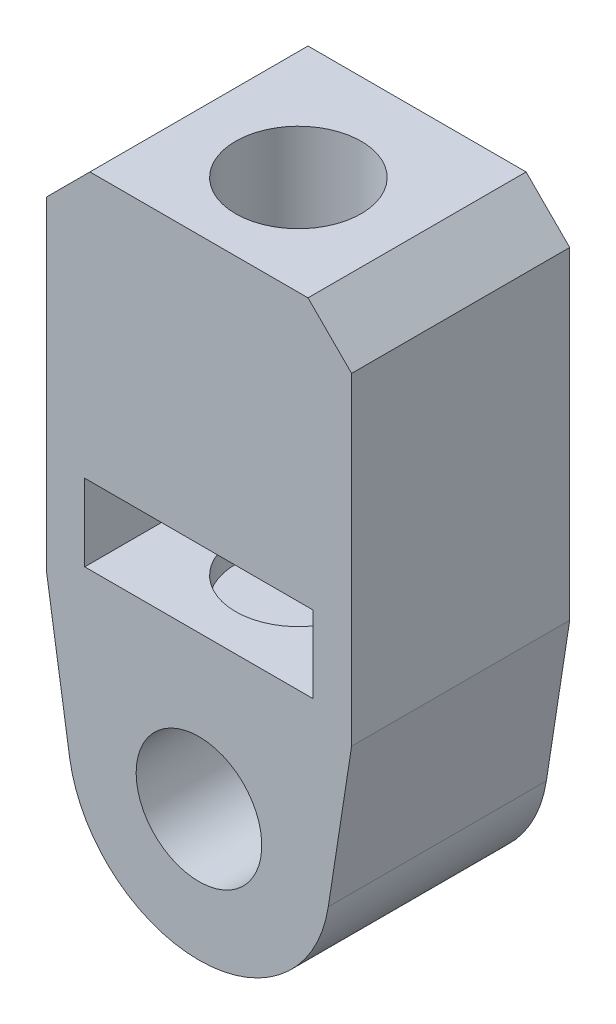
SolidWorks part; units mm, degrees
ref_plane "Front Plane" through (0, 0, 0) normal (0, 0, 1) x (1, 0, 0)
ref_plane "Top Plane" through (0, 0, 0) normal (0, 1, 0) x (1, 0, 0)
ref_plane "Right Plane" through (0, 0, 0) normal (1, 0, 0) x (0, 0, -1)
sketch "Sketch1" plane through (0, 0, 0) normal (0, 0, 1) x (1, 0, 0)
  line L0 (-5.5562, 4.7625) -> (-5.5562, 18.0975)
  line L1 (-5.5562, 18.0975) -> (5.5562, 18.0975)
  line L2 (5.5562, 18.0975) -> (5.5562, 4.7625)
  line L3 (-5.5562, 4.7625) -> (-4.7065, -0.7284)
  line L4 (4.7065, -0.7284) -> (5.5562, 4.7625)
  circle A1 centre (0, 0) radius 2.286
  arc A2 (-4.7065, -0.7284) -> (4.7065, -0.7284) centre (0, 0) ccw
  point P10 (0, 18.0975)
  dimension "D1" = 9.525
  dimension "D2" = 4.572
  dimension "D3" = 13.335
  dimension "D4" = 11.1125
  dimension "D5" = 4.7625
extrude "Boss-Extrude1" add sketch "Sketch1" along normal up to surface (7.9375 mm away)
sketch "Sketch2" plane through (0, 18.0975, 0) normal (0, 1, 0) x (1, 0, 0)
  circle A1 centre (0, -4.3187) radius 2.286
  circle A2 centre (0, -4.3187) radius 1.7525 construction
  dimension "D1" = 4.572
extrude "Cut-Extrude1" cut sketch "Sketch2" against normal offset from surface (13.335 mm away) 4.7625 up to plane "Top Plane"
sketch "Sketch3" plane through (0, 4.7625, 0) normal (0, 1, 0) x (1, 0, 0)
  line L11 (5.5562, -7.9375) -> (-5.5562, -7.9375) construction
  line L12 (-1.9064, -1.0167) -> (-4.1565, -4.9141)
  line L16 (4.1565, -4.9141) -> (1.9064, -1.0167)
  line L17 (1.9064, -1.0167) -> (-1.9064, -1.0167)
  line L18 (-4.1565, -4.9141) -> (-4.1565, -7.9375)
  line L19 (-4.1565, -7.9375) -> (4.1565, -7.9375)
  line L20 (4.1565, -7.9375) -> (4.1565, -4.9141)
  line L22 (-1.9064, -7.6207) -> (0, -7.6207) [skipped]
  line L23 (-3.8128, -4.3187) -> (-2.8596, -5.9697) [skipped]
  line L24 (2.1818, -7.1438) -> (2.8596, -5.9697) [skipped]
  circle A0 centre (0, -4.3187) radius 3.302 construction
  dimension "D1" = 6.604
extrude "Cut-Extrude2" cut sketch "Sketch3" along normal blind 2.794 from offset 0.7937
chamfer "Chamfer1" distance 1.5875 angle 45 2 edges at (5.5562, 18.0975, 3.9687) (-5.5562, 18.0975, 3.9687)
